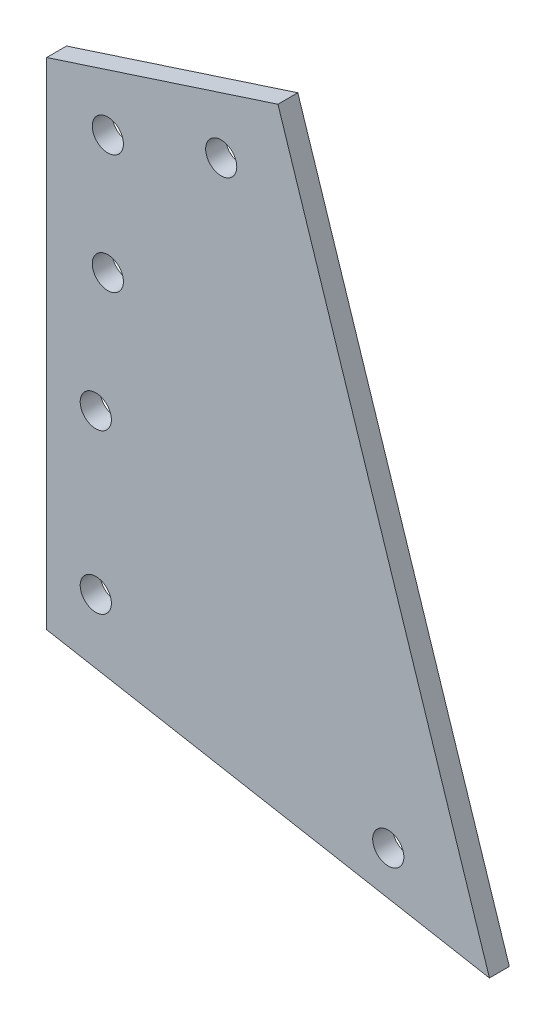
SolidWorks part; units mm, degrees
ref_plane "Front Plane" through (0, 0, 0) normal (0, 0, 1) x (1, 0, 0)
ref_plane "Top Plane" through (0, 0, 0) normal (0, 1, 0) x (1, 0, 0)
ref_plane "Right Plane" through (0, 0, 0) normal (1, 0, 0) x (0, 0, -1)
sketch "Sketch2" plane through (0, 0, 0) normal (0, 0, 1) x (1, 0, 0)
  line L0 (40.992, 297.6034) -> (41.8057, 295.099) construction
  line L2 (40.992, 297.6034) -> (52.5693, 261.972) construction
  line L6 (201.5046, -196.4039) -> (40.992, 297.6034) construction
  line L7 (75.6024, 191.0833) -> (41.8057, 295.099)
  line L8 (4.8542, 283.0927) -> (4.8542, 203.9015)
  line L9 (4.8542, 203.9015) -> (75.6024, 191.0833)
  line L10 (12.7, 238.125) -> (12.7, 212.725) construction
  line L11 (52.3102, 180.5731) -> (64.7523, 184.6158) construction
  line L12 (177.3478, -204.253) -> (25.4, 263.3943) construction
  line L13 (64.7523, 184.6158) -> (29.6006, 292.8015) construction
  line L14 (41.8057, 295.099) -> (4.8542, 283.0927)
  dimension "D1" = 109.3686
extrude "Boss-Extrude1" add sketch "Sketch2" along normal blind 3.175
sketch "Sketch3" plane through (0, 0, 3.175) normal (0, 0, 1) x (1, 0, 0)
  line L0 (75.6024, 191.0833) -> (63.8876, 187.2769) construction
  line L1 (63.8876, 187.2769) -> (29.6006, 292.8015) construction
  line L3 (61.8407, 193.5766) -> (59.4352, 200.9803) construction
  line L4 (4.8542, 203.9015) -> (75.6024, 191.0833) construction
  line L5 (29.6006, 292.8015) -> (32.7403, 283.1387) construction
  line L6 (32.7403, 283.1387) -> (14.6226, 277.2519) construction
  line L7 (14.6226, 277.2519) -> (14.6226, 258.2019) construction
  dimension "D1" = 86.3865
hole_wizard "#10 Clearance Hole1" positions "Sketch4" profile "Sketch5" hole size "#10" standard "ANSI Inch" end condition through all
sketch "Sketch4" plane through (0, 0, 3.175) normal (0, 0, 1) x (1, 0, 0)
  point P0 (32.7403, 283.1387)
  point P3 (59.4352, 200.9803)
  point P7 (12.7, 238.125)
  point P10 (12.7, 212.725)
  point P14 (14.6226, 277.2519)
  point P17 (14.6226, 258.2019)
sketch "Sketch5" plane through (32.7403, 283.1387, 3.175) normal (1, 0, 0) x (0, -1, 0)
  line L0 (0, 0) -> (0, 3.175)
  line L1 (0, 3.175) -> (2.4892, 3.175)
  line L2 (2.4892, 3.175) -> (2.4892, 0)
  line L5 (2.4892, 0) -> (0, 0)
  line L11 (0, -6.35) -> (0, 107.95) construction
  dimension "Thru Hole Dia." = 4.9784
  dimension "Thru Hole Depth" = 3.175
